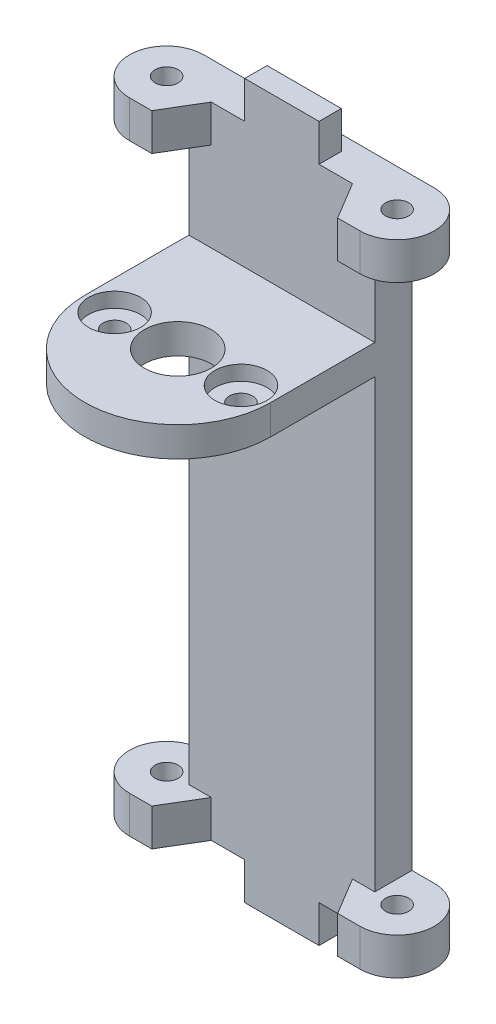
SolidWorks part; units mm, degrees
ref_plane "Front Plane" through (0, 0, 0) normal (0, 0, 1) x (1, 0, 0)
ref_plane "Top Plane" through (0, 0, 0) normal (0, 1, 0) x (1, 0, 0)
ref_plane "Right Plane" through (0, 0, 0) normal (1, 0, 0) x (0, 0, -1)
sketch "Sketch11" plane through (0, 0, 51.65) normal (0, -1, 0) x (1, 0, 0)
  line L0 (12.5, 85.5) -> (12.5, 71.5)
  line L1 (-12.5, 85.5) -> (-12.5, 71.5)
  line L3 (0, 71.5) -> (0, 85.5) construction
  line L6 (-12.5, 71.5) -> (12.5, 71.5)
  line L7 (-8.5, 85.5) -> (8.5, 85.5) construction
  circle A0 centre (-8.5, 85.5) radius 1.55
  circle A1 centre (8.5, 85.5) radius 1.55
  circle A4 centre (0, 85.5) radius 4.5
  arc A5 (-12.5, 85.5) -> (12.5, 85.5) centre (0, 85.5) cw
  point P15 (0, 85.5)
extrude "Boss-Extrude1" add sketch "Sketch11" along normal blind 4
sketch "Sketch12" plane through (0, 0, 123.15) normal (0, 0, -1) x (-1, 0, 0)
  line L0 (-12.5, 0) -> (-12.5, 17)
  line L1 (12.5, 0) -> (12.5, 17)
  line L3 (-12.5, 0) -> (-12.5, -4)
  line L4 (-12.5, -4) -> (-12.5, -69)
  line L5 (12.5, 0) -> (12.5, -4)
  line L6 (12.5, -4) -> (12.5, -69)
  line L20 (-12.5, 17) -> (12.5, 17)
  line L21 (-12.5, -69) -> (12.5, -69)
extrude "Boss-Extrude2" add sketch "Sketch12" along normal blind 5
sketch "Sketch13" plane through (0, 0, 0) normal (0, 1, 0) x (1, 0, 0)
  circle A0 centre (-8.5, -137.15) radius 3.5
  circle A1 centre (8.5, -137.15) radius 3.5
extrude "Cut-Extrude1" cut sketch "Sketch13" against normal blind 2
ref_plane "Plane1" through (0, 17, 0) normal (0, 1, 0) x (1, 0, 0)
sketch "Sketch14" plane through (0, 17, 0) normal (0, 1, 0) x (1, 0, 0)
  line L0 (12.5, -123.15) -> (15.5, -123.15) construction
  line L1 (-12.5, -137.15) -> (-12.5, -123.15) construction
  line L2 (-12.5, -123.15) -> (-15.5, -123.15) construction
  line L4 (12.5, -123.15) -> (12.5, -137.15) construction
  line L6 (15.5, -118.15) -> (-15.5, -118.15)
  line L7 (-15.5, -128.15) -> (-12.5, -128.15)
  line L11 (12.5, -128.15) -> (15.5, -128.15)
  line L12 (-12.5, -128.15) -> (-9.5, -123.15)
  line L13 (12.5, -128.15) -> (9.5, -123.15)
  line L15 (-12.5, -123.15) -> (12.5, -123.15) construction
  line L16 (9.5, -123.15) -> (-9.5, -123.15)
  arc A0 (-15.5, -118.15) -> (-15.5, -128.15) centre (-15.5, -123.15) ccw
  circle A1 centre (-15.5, -123.15) radius 1.55
  circle A2 centre (15.5, -123.15) radius 1.55
  arc A3 (15.5, -118.15) -> (15.5, -128.15) centre (15.5, -123.15) cw
extrude "Boss-Extrude3" add sketch "Sketch14" against normal blind 5
ref_plane "Plane2" through (0, -69, 0) normal (0, -1, 0) x (-1, 0, 0)
sketch "Sketch15" plane through (0, -69, 0) normal (0, -1, 0) x (-1, 0, 0)
  line L0 (15.5, -128.15) -> (12.5, -128.15) construction
  line L1 (15.5, -118.15) -> (-15.5, -118.15)
  line L2 (-15.5, -128.15) -> (-12.5, -128.15)
  line L3 (-12.5, -128.15) -> (-9.5, -123.15)
  line L5 (15.5, -128.15) -> (12.5, -128.15)
  line L6 (12.5, -128.15) -> (9.5, -123.15)
  line L8 (9.5, -123.15) -> (-9.5, -123.15)
  circle A0 centre (15.5, -123.15) radius 1.55
  circle A1 centre (-15.5, -123.15) radius 1.55
  arc A2 (15.5, -118.15) -> (15.5, -128.15) centre (15.5, -123.15) cw
  arc A3 (-15.5, -118.15) -> (-15.5, -128.15) centre (-15.5, -123.15) ccw
  arc A4 (-15.5, -118.15) -> (-15.5, -128.15) centre (-15.5, -123.15) ccw construction
extrude "Boss-Extrude4" add sketch "Sketch15" against normal blind 5
sketch "Sketch16" plane through (0, -69, 0) normal (0, -1, 0) x (1, 0, 0)
  line L0 (-5, 123.15) -> (5, 123.15)
  line L1 (-5, 123.15) -> (-5, 120.15)
  line L2 (-12.5, 123.15) -> (12.5, 123.15) construction
  line L5 (-5, 120.15) -> (5, 120.15)
  line L6 (5, 123.15) -> (5, 120.15)
  point P3 (0, 123.15)
extrude "Boss-Extrude5" add sketch "Sketch16" along normal blind 5
sketch "Sketch17" plane through (0, 17, 0) normal (0, 1, 0) x (1, 0, 0)
  line L0 (-5, -123.15) -> (5, -123.15)
  line L1 (-9.5, -123.15) -> (9.5, -123.15) construction
  line L2 (-5, -123.15) -> (-5, -120.15)
  line L3 (-5, -120.15) -> (5, -120.15)
  line L4 (5, -120.15) -> (5, -123.15)
  point P5 (0, -123.15)
extrude "Boss-Extrude6" add sketch "Sketch17" along normal blind 5
